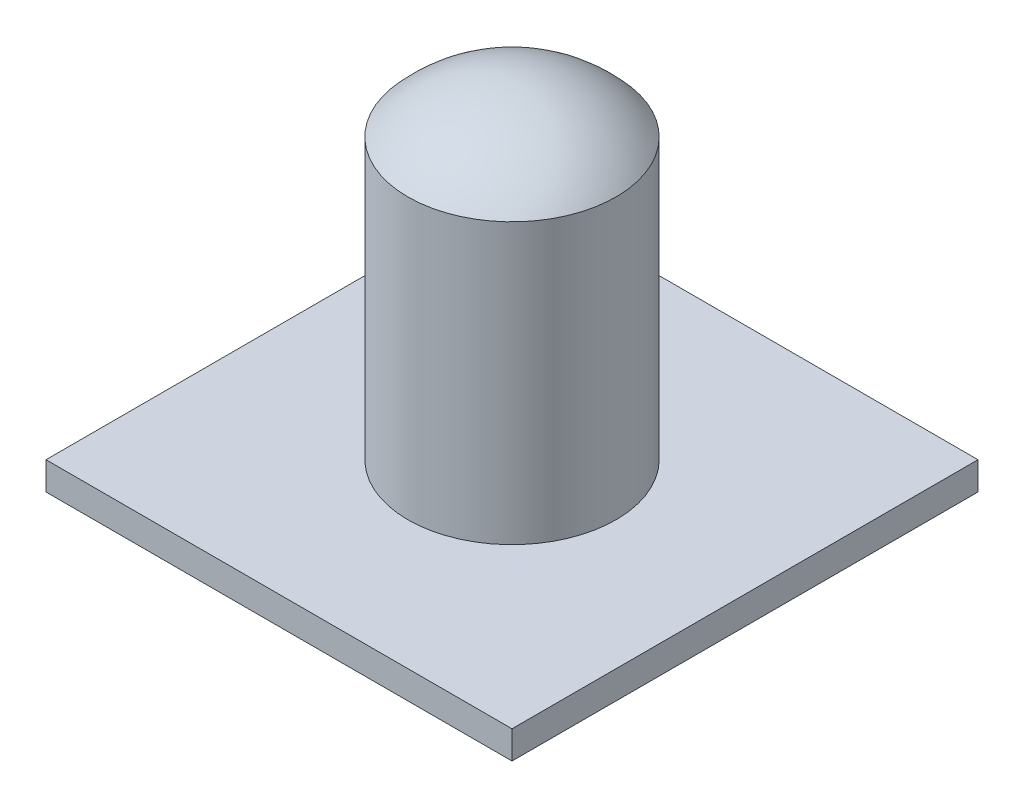
SolidWorks part; units mm, degrees
ref_plane "Front Plane" through (0, 0, 0) normal (0, 0, 1) x (1, 0, 0)
ref_plane "Top Plane" through (0, 0, 0) normal (0, 1, 0) x (1, 0, 0)
ref_plane "Right Plane" through (0, 0, 0) normal (1, 0, 0) x (0, 0, -1)
sketch "Sketch3" plane through (0, 0, 0) normal (0, 1, 0) x (1, 0, 0)
  line L0 (-19.05, -19.05) -> (19.05, -19.05)
  line L1 (19.05, -19.05) -> (19.05, 19.05)
  line L2 (19.05, 19.05) -> (-19.05, 19.05)
  line L3 (-19.05, 19.05) -> (-19.05, -19.05)
  point P4 (0, 19.05)
  dimension "D1" = 38.1
  dimension "D2" = 38.1
  dimension "D3" = 19.05
  dimension "D4" = 19.05
extrude "Boss-Extrude1" add sketch "Sketch3" along normal blind 2.286
sketch "Sketch4" plane through (0, 2.286, 0) normal (0, 1, 0) x (1, 0, 0)
  circle A0 centre (0, 0) radius 8.509
  dimension "D1" = 17.018
extrude "Boss-Extrude2" add sketch "Sketch4" along normal blind 22.86
dome "Dome2" faces to dome 1 distance 3.81 reverse direction no elliptical dome no face at (0, 25.146, 8.509) parameters "D1"=3.81
